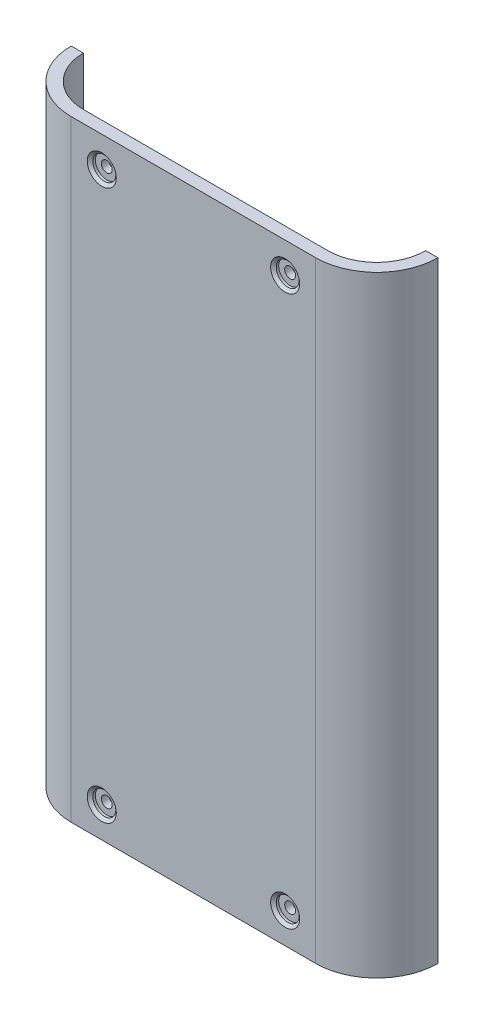
SolidWorks part; units mm, degrees
material "A-Glass Fiber"
ref_plane "Front Plane" through (0, 0, 0) normal (0, 0, 1) x (1, 0, 0)
ref_plane "Top Plane" through (0, 0, 0) normal (0, 1, 0) x (1, 0, 0)
ref_plane "Right Plane" through (0, 0, 0) normal (1, 0, 0) x (0, 0, -1)
sketch "Sketch1" plane through (0, 0, 0) normal (0, 1, 0) x (1, 0, 0)
  line L1 (-38.1, 38.1) -> (38.1, 38.1)
  line L2 (-38.1, 38.1) -> (-38.1, -38.1)
  line L3 (-38.1, -38.1) -> (38.1, -38.1)
  line L4 (38.1, 38.1) -> (38.1, -38.1)
  line L5 (-38.1, 38.1) -> (38.1, -38.1) construction
  line L6 (-38.1, -38.1) -> (38.1, 38.1) construction
  point P0 (0, 0)
  dimension "D1" = 76.2
  dimension "D2" = 76.2
extrude "Boss-Extrude1" add sketch "Sketch1" along normal blind 127
sketch "Sketch2" plane through (0, 127, 0) normal (0, 1, 0) x (1, 0, 0)
  line L0 (-38.1, 6.35) -> (38.1, 6.35)
  line L1 (-38.1, 38.1) -> (-38.1, -38.1) construction
  line L2 (38.1, -38.1) -> (38.1, 38.1) construction
  line L3 (-38.1, -6.35) -> (38.1, -6.35)
  line L4 (-38.1, 6.35) -> (-38.1, -6.35)
  line L5 (38.1, 6.35) -> (38.1, -6.35)
  dimension "D1" = 6.35
  dimension "D2" = 6.35
fillet "Fillet1" radius 12.7 4 edges at (38.1, 63.5, 38.1) (38.1, 63.5, -38.1) (-38.1, 63.5, -38.1) (-38.1, 63.5, 38.1)
extrude "Boss-Extrude6" add sketch "Sketch2" along normal blind 57.15
sketch "Sketch5" plane through (0, 0, 6.35) normal (0, 0, 1) x (1, 0, 0)
  line L0 (-27.94, 127) -> (27.94, 127)
  line L1 (0, 184.15) -> (0, 146.05)
  line L4 (-38.1, 184.15) -> (38.1, 184.15) construction
  line L5 (-38.1, 184.15) -> (-38.1, 127) construction
  line L6 (38.1, 184.15) -> (38.1, 127) construction
  line L7 (-38.1, 146.05) -> (-27.94, 146.05)
  line L8 (27.94, 146.05) -> (27.94, 127)
  line L9 (-38.1, 127) -> (38.1, 127) construction
  line L10 (27.94, 127) -> (38.1, 127)
  line L11 (38.1, 127) -> (38.1, 146.05)
  line L12 (-38.1, 146.05) -> (-38.1, 127)
  line L13 (-38.1, 127) -> (-27.94, 127)
  line L14 (-27.94, 127) -> (-27.94, 146.05)
  line L15 (-27.94, 146.05) -> (27.94, 146.05)
  line L16 (0, 146.05) -> (0, 152.4937)
  line L17 (0, 152.4937) -> (27.1868, 152.4937)
  line L18 (0, 152.4937) -> (-27.1868, 152.4937)
  arc A0 (-38.1, 146.05) -> (38.1, 146.05) centre (0, 146.05) cw
  arc A1 (-27.94, 146.05) -> (27.94, 146.05) centre (0, 146.05) cw
  arc A2 (-27.94, 146.05) -> (-27.1868, 152.4937) centre (0, 146.05) cw
  arc A3 (27.94, 146.05) -> (27.1868, 152.4937) centre (0, 146.05) ccw
  arc A4 (0, 146.05) -> (-27.94, 127) centre (0, 116.0357) ccw
  arc A5 (0, 146.05) -> (27.94, 127) centre (0, 116.0357) cw
  arc A6 (0, 148.59) -> (-30.3045, 127.9279) centre (0, 116.0357) ccw
  arc A7 (0, 148.59) -> (30.3045, 127.9279) centre (0, 116.0357) cw
  line M8 (-38.1, 127) -> (38.1, 127)
  line M9 (38.1, 127) -> (38.1, 184.15)
  line M10 (38.1, 184.15) -> (-38.1, 184.15)
  line M11 (-38.1, 184.15) -> (-38.1, 127)
  dimension "D3" = 2.54
  dimension "D4" = 2.54
  dimension "D1" = 38.1
  dimension "D2" = 10.16
extrude "Cut-Extrude2" cut sketch "Sketch5" against normal blind 12.7 contours A0 M11 M10 | A1 L18 L1 | A1 L1 L17 | A6 L15 L14 | L15 A7 L8 | A5 A4 M8 | A0 M10 M9 region at (0, 134.8748, 6.35) region at (-23.417, 142.0913, 6.35) region at (23.417, 142.0913, 6.35) region at (-29.5897, 175.6397, 6.35) region at (29.5897, 175.6397, 6.35) region at (-11.0421, 161.459, 6.35) region at (11.0421, 161.459, 6.35)
sketch "Sketch6" plane through (0, 0, 0) normal (0, -1, 0) x (1, 0, 0)
  line L0 (-38.1, 25.4) -> (38.1, 25.4)
  line L16 (-35.56, 8.89) -> (35.56, 8.89)
  line L17 (-35.56, -8.89) -> (35.56, -8.89)
  line L20 (-35.56, 25.4) -> (-35.56, -25.4)
  line L21 (-25.4, -35.56) -> (25.4, -35.56)
  line L22 (35.56, -25.4) -> (35.56, 25.4)
  line L23 (25.4, 35.56) -> (-25.4, 35.56)
  line L24 (-35.56, 25.4) -> (-35.56, -25.4)
  line L25 (-25.4, -35.56) -> (25.4, -35.56)
  line L26 (35.56, -25.4) -> (35.56, 25.4)
  line L27 (25.4, 35.56) -> (-25.4, 35.56)
  circle A0 centre (0, 0) radius 6.35
  arc A25 (-35.56, -25.4) -> (-25.4, -35.56) centre (-25.4, -25.4) ccw
  arc A26 (25.4, -35.56) -> (35.56, -25.4) centre (25.4, -25.4) ccw
  arc A27 (35.56, 25.4) -> (25.4, 35.56) centre (25.4, 25.4) ccw
  arc A28 (-25.4, 35.56) -> (-35.56, 25.4) centre (-25.4, 25.4) ccw
  arc A29 (-35.56, -25.4) -> (-25.4, -35.56) centre (-25.4, -25.4) ccw
  arc A30 (25.4, -35.56) -> (35.56, -25.4) centre (25.4, -25.4) ccw
  arc A31 (35.56, 25.4) -> (25.4, 35.56) centre (25.4, 25.4) ccw
  arc A32 (-25.4, 35.56) -> (-35.56, 25.4) centre (-25.4, 25.4) ccw
  point P5 (0, 8.89)
  line M11 (38.1, -25.4) -> (38.1, 25.4)
  line M15 (-38.1, 25.4) -> (-38.1, -25.4)
  arc M16 (-38.1, -25.4) -> (-25.4, -38.1) centre (-25.4, -25.4) ccw
  line M17 (-25.4, -38.1) -> (25.4, -38.1)
  arc M18 (25.4, -38.1) -> (38.1, -25.4) centre (25.4, -25.4) ccw
  dimension "D1" = 12.7
  dimension "D3" = 8.89
  dimension "D4" = 8.89
  dimension "D2" = 2.54
extrude "Cut-Extrude4" cut sketch "Sketch6" against normal blind 254 contours L16 L26 L0 L24 | A30 L25 A29 L24 L0 L26 M15 M16 M17 M18 M11 | L17 L26 L16 L24 A0 | A0 | L25 A30 L26 L17 L24 A29 region at (-36.83, 0, 24.4081) region at (0, 0, 17.145) region at (0, 0, 8.1569) region at (0, 0, -21.9603) region at (0, 0, 0)
sketch "Sketch7" plane through (0, 0, 0) normal (0, -1, 0) x (1, 0, 0)
  line L0 (-35.56, 25.4) -> (-25.4, 25.4)
  line L1 (-25.4, 35.56) -> (-25.4, 25.4)
  line L2 (-25.4, 35.56) -> (25.4, 35.56)
  line L3 (-25.4, 35.56) -> (25.4, 35.56)
  line L4 (-25.4, 25.4) -> (25.4, 25.4)
  line L5 (-38.1, 25.4) -> (38.1, 25.4) construction
  line L6 (25.4, 25.4) -> (25.4, 35.56)
  line L7 (25.4, 25.4) -> (35.56, 25.4)
  arc A3 (-25.4, 35.56) -> (-35.56, 25.4) centre (-25.4, 25.4) ccw
  arc A4 (-25.4, 35.56) -> (-35.56, 25.4) centre (-25.4, 25.4) ccw
  arc A6 (35.56, 25.4) -> (25.4, 35.56) centre (25.4, 25.4) ccw
  arc A7 (35.56, 25.4) -> (25.4, 35.56) centre (25.4, 25.4) ccw
  line M2 (-38.1, 25.4) -> (38.1, 25.4)
  dimension "D1" = 2.54
  dimension "D2" = 2.54
  dimension "D3" = 2.54
extrude "Cut-Extrude7" cut sketch "Sketch7" against normal blind 124.46 contours L6 L3 L1 M2 region at (0, 0, 30.48)
extrude "Cut-Extrude8" cut sketch "Sketch7<6>" against normal blind 114.3 contours L1 A4 M2 | A7 L6 M2 region at (-29.712, 0, 29.712) region at (29.712, 0, 29.712)
sketch "Sketch7<6>" plane through (0, 0, 0) normal (0, -1, 0) x (1, 0, 0) same geometry as "Sketch7"
extrude "Boss-Extrude7" add sketch "Sketch7<7>" against normal blind 12.7 contours L1 A4 M2 | A7 L6 M2 region at (-29.712, 0, 29.712) region at (29.712, 0, 29.712)
sketch "Sketch7<7>" plane through (0, 0, 0) normal (0, -1, 0) x (1, 0, 0) same geometry as "Sketch7"
extrude "Cut-Extrude9" cut sketch "Sketch7<8>" against normal blind 127 contours A7 L6 M2 | L6 L3 L1 M2 | L1 A4 M2 region at (-29.712, 0, 29.712) region at (0, 0, 30.48) region at (29.712, 0, 29.712)
sketch "Sketch7<8>" plane through (0, 0, 0) normal (0, -1, 0) x (1, 0, 0) same geometry as "Sketch7"
sketch "Sketch11" plane through (0, 0, 38.1) normal (0, 0, 1) x (1, 0, 0)
  point P30 (-19.05, 120.65)
  point P34 (19.05, 120.65)
  point P41 (-19.05, 6.35)
  point P44 (19.05, 6.35)
hole_wizard "CBORE for #1 Binding Head Machine Screw1" positions "Sketch11" profile "Sketch12" counterbore size "#1" standard "ANSI Inch"
sketch "Sketch12" plane through (-19.05, 120.65, 38.1) normal (1, 0, 0) x (0, -1, 0)
  line L0 (0, 0) -> (0, 10.8392)
  line L1 (0, 10.8392) -> (1.1303, 10.16)
  line L2 (1.1303, 10.16) -> (1.1303, 1.0414)
  line L3 (1.1303, 1.0414) -> (2.3812, 1.0414)
  line L5 (2.3812, 1.0414) -> (2.3813, 0.5328)
  line L6 (2.3813, 0.5328) -> (3.0162, 0)
  line L7 (3.0162, 0) -> (0, 0)
  line L8 (-2.3813, 0.5328) -> (-3.0162, 0) construction
  line L10 (0, 10.8392) -> (-1.1303, 10.16) construction
  line L11 (0, -6.35) -> (0, 107.95) construction
  dimension "Hole Dia." = 2.2606
  dimension "Hole Depth" = 10.16
  dimension "C'Bore Dia." = 4.7625
  dimension "C'Bore Depth" = 1.0414
  dimension "Near C'Sink Dia." = 6.0325
  dimension "Near C'Sink Angle" = 100
  dimension "Drill Angle" = 118
